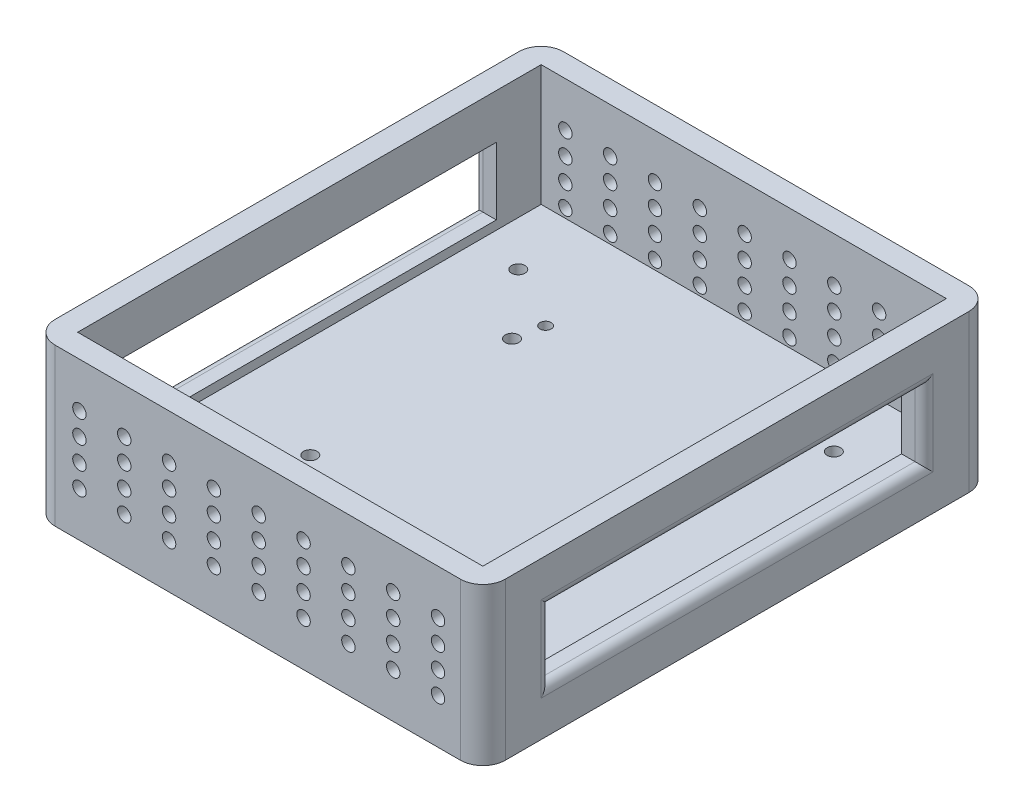
SolidWorks part; units mm, degrees
ref_plane "Front Plane" through (0, 0, 0) normal (0, 0, 1) x (1, 0, 0)
ref_plane "Top Plane" through (0, 0, 0) normal (0, 1, 0) x (1, 0, 0)
ref_plane "Right Plane" through (0, 0, 0) normal (1, 0, 0) x (0, 0, -1)
sketch "Sketch1" plane through (0, 0, 0) normal (0, 1, 0) x (1, 0, 0)
  line L1 (-50.2, -56.7) -> (50.2, -56.7)
  line L2 (-50.2, -56.7) -> (-50.2, 56.7)
  line L3 (-50.2, 56.7) -> (50.2, 56.7)
  line L4 (50.2, -56.7) -> (50.2, 56.7)
  line L5 (-50.2, -56.7) -> (50.2, 56.7) construction
  line L6 (-50.2, 56.7) -> (50.2, -56.7) construction
  point P0 (0, 0)
  dimension "D1" = 100.4
  dimension "D2" = 113.4
extrude "Boss-Extrude2" add sketch "Sketch1" along normal blind 35 contours L3 L4 L1 L2
sketch "Sketch2" plane through (0, 35, 0) normal (0, 1, 0) x (1, 0, 0)
  line L1 (-45.2, -51.7) -> (45.2, -51.7)
  line L2 (-45.2, -51.7) -> (-45.2, 51.7)
  line L3 (-45.2, 51.7) -> (45.2, 51.7)
  line L4 (45.2, -51.7) -> (45.2, 51.7)
  line L5 (-45.2, -51.7) -> (45.2, 51.7) construction
  line L6 (-45.2, 51.7) -> (45.2, -51.7) construction
  point P0 (0, 0)
  dimension "D1" = 103.4
  dimension "D2" = 90.4
extrude "Cut-Extrude1" cut sketch "Sketch2" against normal blind 27
fillet "Fillet4" radius 5 4 edges at (50.2, 17.5, -56.7) (-50.2, 17.5, -56.7) (-50.2, 17.5, 56.7) (50.2, 17.5, 56.7)
sketch "Sketch3" plane through (0, 0, -56.7) normal (0, 0, -1) x (-1, 0, 0)
  line L0 (45.2, 0) -> (-45.2, 0) construction
  line L1 (-50.2, 0) -> (-50.2, 35) construction
  circle A0 centre (-40.2, 10) radius 1.5
  dimension "D1" = 10
  dimension "D2" = 10
sketch "Sketch4" plane through (50.2, 0, 0) normal (1, 0, 0) x (0, 0, -1)
  line L0 (-56.7, 0) -> (-56.7, 35) construction
  line L1 (-41.7, 25) -> (41.7, 25)
  line L2 (-41.7, 25) -> (-41.7, 10)
  line L3 (-41.7, 10) -> (41.7, 10)
  line L4 (41.7, 25) -> (41.7, 10)
  line L6 (-51.7, 0) -> (51.7, 0) construction
  dimension "D1" = 83.4
  dimension "D2" = 15
  dimension "D3" = 10
  dimension "D4" = 15
extrude "Cut-Extrude3" cut sketch "Sketch4" against normal blind 123
fillet "Fillet5" radius 2 4 edges at (50.2, 17.5, 41.7) (50.2, 25, 0) (50.2, 17.5, -41.7) (50.2, 10, 0)
fillet "Fillet6" radius 2 4 edges at (-50.2, 17.5, 41.7) (-50.2, 25, 0) (-50.2, 17.5, -41.7) (-50.2, 10, 0)
extrude "Cut-Extrude4" cut sketch "Sketch3" against normal blind 123 contours A0
pattern_linear "LPattern3" count 9 spacing 10 along (-1, 0, 0) count 4 spacing 5 along (0, 1, 0) of "Cut-Extrude4"
sketch "Sketch5" plane through (0, 8, 0) normal (0, 1, 0) x (1, 0, 0)
  line L0 (-50.2, -51.7) -> (-50.2, 51.7) construction
  line L1 (-45.2, -56.7) -> (45.2, -56.7) construction
  circle A0 centre (-22.5, 22.5) radius 1.5
  circle A1 centre (22.5, 22.5) radius 1.5
  circle A2 centre (-22.5, -22.5) radius 1.5
  circle A3 centre (22.5, -22.5) radius 1.5
  dimension "D1" = 45
  dimension "D2" = 45
  dimension "D3" = 45
  dimension "D4" = 45
  dimension "D5" = 27.7
  dimension "D6" = 34.2
extrude "Cut-Extrude5" cut sketch "Sketch5" against normal blind 37
sketch "Sketch6" plane through (0, 0, 0) normal (0, -1, 0) x (1, 0, 0)
  circle A0 centre (-22.5, 22.5) radius 3
  circle A1 centre (-22.5, -22.5) radius 3
  circle A2 centre (22.5, 22.5) radius 3
  circle A3 centre (22.5, -22.5) radius 3
extrude "Cut-Extrude6" cut sketch "Sketch6" against normal blind 4
sketch "Sketch7" plane through (0, 0, 0) normal (0, -1, 0) x (1, 0, 0)
  line L0 (-45.2, 56.7) -> (45.2, 56.7) construction
  line L1 (50.2, 51.7) -> (50.2, -51.7) construction
  circle A0 centre (-21.25, 28.75) radius 1.25
  circle A1 centre (-21.25, -28.75) radius 1.25
  circle A2 centre (21.25, -28.75) radius 1.25
  circle A3 centre (21.25, 28.75) radius 1.25
  dimension "D1" = 42.5
  dimension "D2" = 42.5
  dimension "D3" = 57.5
  dimension "D4" = 57.5
  dimension "D5" = 27.95
  dimension "D6" = 28.95
  dimension "D7" = 28.95
extrude "Cut-Extrude7" cut sketch "Sketch7" against normal blind 17
sketch "Sketch8" plane through (0, 8, 0) normal (0, 1, 0) x (1, 0, 0)
  line L0 (-45.2, -56.7) -> (45.2, -56.7) construction
  line L1 (-50.2, -51.7) -> (-50.2, 51.7) construction
  circle A0 centre (-35.2, 36.6) radius 1.5
  circle A1 centre (35.2, 36.6) radius 1.5
  circle A2 centre (-35.2, -36.7) radius 1.5
  circle A3 centre (35.2, -36.7) radius 1.5
  dimension "D1" = 73.3
  dimension "D2" = 73.3
  dimension "D3" = 70.4
  dimension "D4" = 70.4
  dimension "D5" = 20
  dimension "D6" = 15
extrude "Cut-Extrude8" cut sketch "Sketch8" against normal blind 9
sketch "Sketch9" plane through (0, 0, 0) normal (0, -1, 0) x (1, 0, 0)
  circle A0 centre (-35.2, 36.7) radius 3
  circle A1 centre (35.2, 36.7) radius 3
  circle A2 centre (-35.2, -36.6) radius 3
  circle A3 centre (35.2, -36.6) radius 3
extrude "Cut-Extrude9" cut sketch "Sketch9" against normal blind 4
